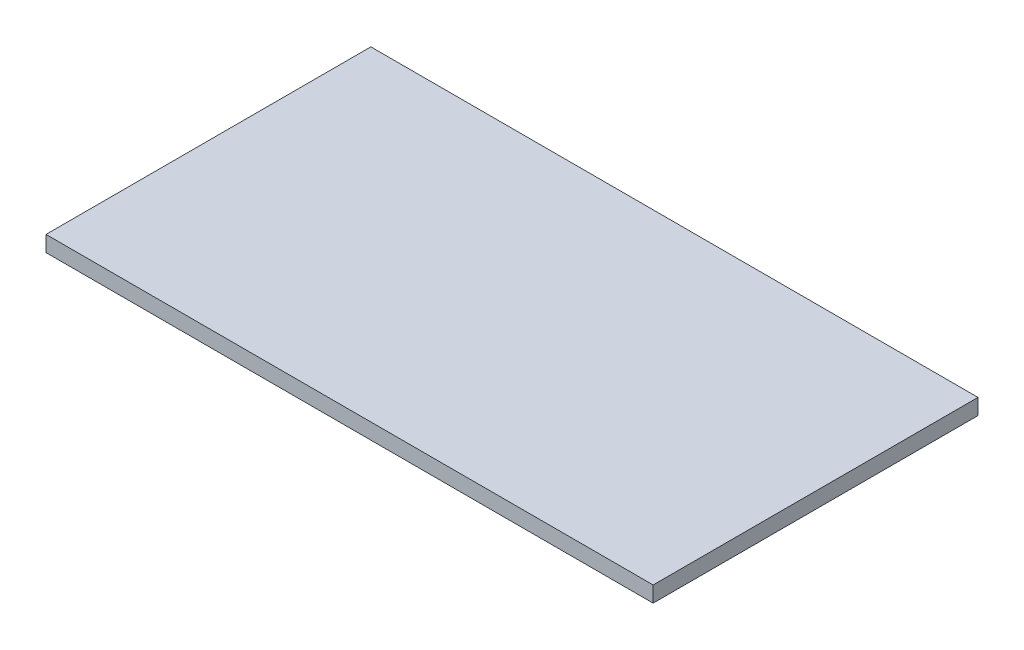
SolidWorks part; units mm, degrees
ref_plane "Front Plane" through (0, 0, 0) normal (0, 0, 1) x (1, 0, 0)
ref_plane "Top Plane" through (0, 0, 0) normal (0, 1, 0) x (1, 0, 0)
ref_plane "Right Plane" through (0, 0, 0) normal (1, 0, 0) x (0, 0, -1)
sketch "Sketch1" plane through (0, 0, 0) normal (0, 1, 0) x (1, 0, 0)
  line L0 (-1925, 1030) -> (1925, 1030)
  line L1 (-1825, -930) -> (1825, -930)
  line L2 (-1825, -930) -> (-1825, 930)
  line L3 (-1825, 930) -> (1825, 930)
  line L4 (1825, -930) -> (1825, 930)
  line L5 (-1825, -930) -> (1825, 930) construction
  line L6 (-1825, 930) -> (1825, -930) construction
  line L7 (1925, -1030) -> (1925, 1030)
  line L8 (-1925, -1030) -> (1925, -1030)
  line L9 (-1925, -1030) -> (-1925, 1030)
  point P0 (0, 0)
  dimension "D1" = 3650
  dimension "D2" = 1860
  dimension "D3" = 100
extrude "Boss-Extrude1" add sketch "Sketch1" along normal blind 100 contours L9 L0 L7 L8
extrude "Cut-Extrude4" cut sketch "Sketch1<5>" along normal blind 60 contours L1 L4 L3 L2 region at (0, 0, 0)
sketch "Sketch1<5>" plane through (0, 0, 0) normal (0, 1, 0) x (1, 0, 0) same geometry as "Sketch1"
sketch "Sketch2" plane through (0, 60, 0) normal (0, -1, 0) x (1, 0, 0)
  line L0 (-1088, 930) -> (-1088, -930) construction
  line L1 (-1825, 930) -> (1825, 930) construction
  line L2 (-1825, -930) -> (1825, -930) construction
  line L4 (-1085.5, 930) -> (-1085.5, -930)
  line L5 (-1090.5, 930) -> (-1090.5, 294.4894)
  line L6 (-1825, 930) -> (-1825, -930) construction
  line L7 (-1090.5, 930) -> (-1085.5, 930)
  line L8 (-1085.5, -930) -> (-1090.5, -930)
  line L9 (-1090.5, -294.4894) -> (-1090.5, -930)
  line L10 (-1090.5, 289.4892) -> (-1090.5, -289.4892)
  arc A1 (-1090.5, 294.4894) -> (-1090.5, -294.4894) centre (-1088, 0) ccw
  arc A2 (-1090.5, 289.4892) -> (-1090.5, -289.4892) centre (-1088, 0) ccw
  point P8 (-1088, 0)
  point P9 (-1088, 292)
  point P10 (-1088, -292)
  point P17 (0, 0)
  dimension "D2" = 2.5
  dimension "D4" = 289.5
  dimension "D5" = 294.5
  dimension "D6" = 5
  dimension "D1" = 737
  dimension "D3" = 2.5
